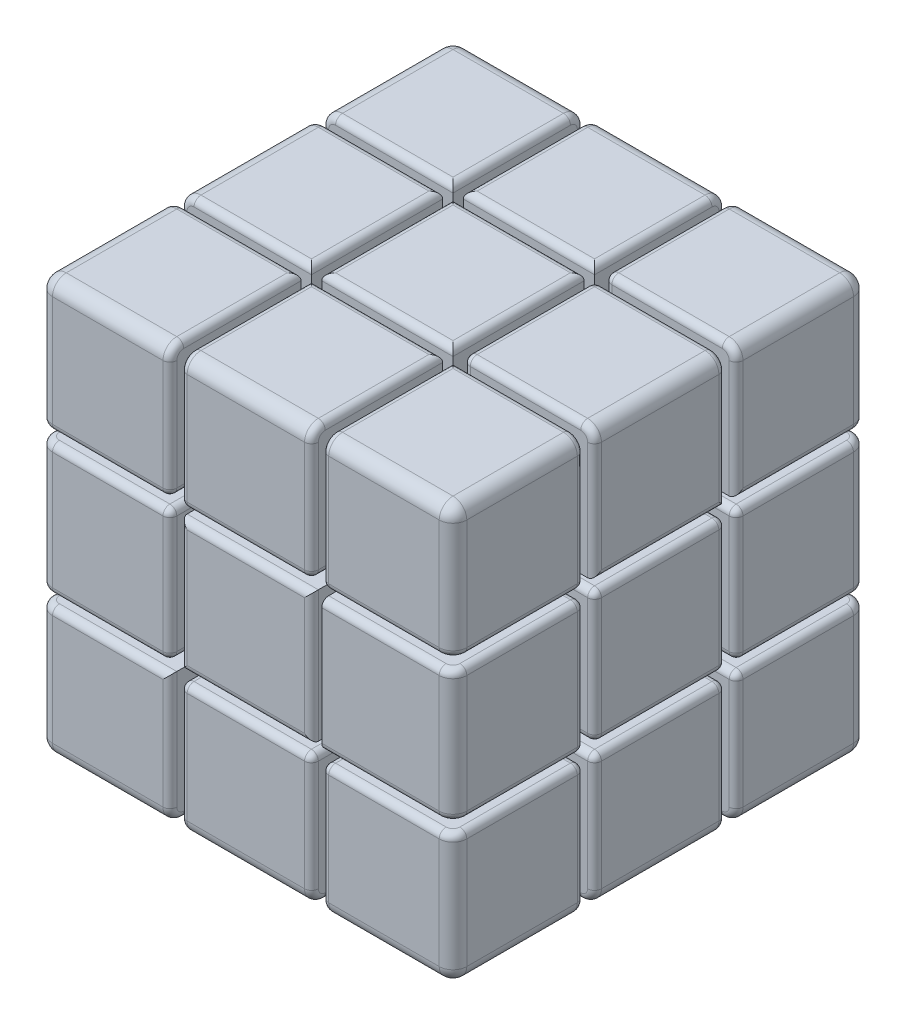
SolidWorks part; units mm, degrees
ref_plane "Front Plane" through (0, 0, 0) normal (0, 0, 1) x (1, 0, 0)
ref_plane "Top Plane" through (0, 0, 0) normal (0, 1, 0) x (1, 0, 0)
ref_plane "Right Plane" through (0, 0, 0) normal (1, 0, 0) x (0, 0, -1)
sketch "Sketch1" plane through (0, 0, 0) normal (0, 1, 0) x (1, 0, 0)
  line L1 (-30, 30) -> (30, 30)
  line L2 (-30, 30) -> (-30, -30)
  line L3 (-30, -30) -> (30, -30)
  line L4 (30, 30) -> (30, -30)
  line L5 (-30, 30) -> (30, -30) construction
  line L6 (-30, -30) -> (30, 30) construction
  point P0 (0, 0)
  dimension "D1" = 60
  dimension "D2" = 60
extrude "Boss-Extrude1" add sketch "Sketch1" along normal blind 60
sketch "Sketch2" plane through (0, 0, 30) normal (0, 0, 1) x (1, 0, 0)
  line L0 (-30, 60) -> (30, 60) construction
  line L1 (-11, 60) -> (-9.5, 60)
  line L2 (-11, 60) -> (-11, 0)
  line L3 (-11, 0) -> (-9.5, 0)
  line L4 (-9.5, 60) -> (-9.5, 0)
  line L5 (-30, 0) -> (30, 0) construction
  line L6 (-30, 60) -> (-30, 0) construction
  line L7 (9.5, 60) -> (11, 60)
  line L8 (9.5, 60) -> (9.5, 0)
  line L9 (9.5, 0) -> (11, 0)
  line L10 (11, 60) -> (11, 0)
  line L11 (-30, 41) -> (30, 41)
  line L12 (-30, 41) -> (-30, 39.5)
  line L13 (-30, 39.5) -> (30, 39.5)
  line L14 (30, 41) -> (30, 39.5)
  line L15 (30, 60) -> (30, 0) construction
  line L17 (-30, 20.5) -> (30, 20.5)
  line L18 (-30, 20.5) -> (-30, 19)
  line L19 (-30, 19) -> (30, 19)
  line L20 (30, 20.5) -> (30, 19)
  dimension "D1" = 1.5
  dimension "D2" = 1.5
  dimension "D3" = 1.5
  dimension "D4" = 1.5
  dimension "D5" = 19
  dimension "D6" = 19
  dimension "D7" = 19
  dimension "D8" = 19
extrude "Cut-Extrude1" cut sketch "Sketch2" against normal blind 60 contours L11 L14 L13 L12 | L2 L3 L4 L1 | L19 L20 L17 L18 | L8 L9 L10 L7
sketch "Sketch3" plane through (30, 0, 0) normal (1, 0, 0) x (0, 0, -1)
  line L0 (-30, 60) -> (30, 60) construction
  line L1 (-9.5, 60) -> (-11, 60)
  line L2 (-9.5, 60) -> (-9.5, 0)
  line L3 (-9.5, 0) -> (-11, 0)
  line L4 (-11, 60) -> (-11, 0)
  line L5 (-30, 0) -> (30, 0) construction
  line L6 (30, 0) -> (-30, 0) construction
  line L7 (9.5, 60) -> (11, 60)
  line L8 (9.5, 60) -> (9.5, 0)
  line L9 (9.5, 0) -> (11, 0)
  line L10 (11, 60) -> (11, 0)
  line L11 (30, 19) -> (30, 0) construction
  dimension "D1" = 19
  dimension "D2" = 1.5
  dimension "D3" = 1.5
  dimension "D4" = 19
extrude "Cut-Extrude2" cut sketch "Sketch3" against normal blind 60
fillet "Fillet1" radius 2 3 edges at (20.5, 60, 30) (30, 50.5, 30) (30, 60, 20.5)
fillet "Fillet2" radius 2 3 edges at (30, 0, 20.5) (20.5, 0, 30) (30, 9.5, 30)
fillet "Fillet3" radius 2 1 edges at (30, 30, 30)
fillet "Fillet4" radius 2 1 edges at (0, 60, 30)
fillet "Fillet5" radius 2 3 edges at (-30, 60, 20.5) (-30, 50.5, 30) (-20.5, 60, 30)
fillet "Fillet6" radius 2 3 edges at (-20.5, 0, 30) (-30, 0, 20.5) (-30, 9.5, 30)
fillet "Fillet7" radius 2 1 edges at (-30, 30, 30)
fillet "Fillet8" radius 2 1 edges at (0, 0, 30)
fillet "Fillet9" radius 2 1 edges at (-30, 60, 0)
fillet "Fillet10" radius 2 3 edges at (-20.5, 60, -30) (-30, 50.5, -30) (-30, 60, -20.5)
fillet "Fillet11" radius 2 1 edges at (-30, 30, -30)
fillet "Fillet12" radius 2 3 edges at (-30, 0, -20.5) (-20.5, 0, -30) (-30, 9.5, -30)
fillet "Fillet13" radius 2 1 edges at (-30, 0, 0)
fillet "Fillet14" radius 2 1 edges at (0, 0, -30)
fillet "Fillet15" radius 2 3 edges at (30, 9.5, -30) (30, 0, -20.5) (20.5, 0, -30)
fillet "Fillet16" radius 2 1 edges at (30, 0, 0)
fillet "Fillet17" radius 2 1 edges at (30, 30, -30)
fillet "Fillet18" radius 2 3 edges at (30, 60, -20.5) (20.5, 60, -30) (30, 50.5, -30)
fillet "Fillet19" radius 2 1 edges at (30, 60, 0)
fillet "Fillet20" radius 2 1 edges at (0, 60, -30)
fillet "Fillet21" radius 1 3 edges at (19.5, 19, 30) (29.4142, 19, 29.4142) (30, 19, 19.5)
fillet "Fillet22" radius 1 1 edges at (30, 19, 0)
fillet "Fillet23" radius 1 3 edges at (19.5, 39.5, 30) (29.4142, 39.5, 29.4142) (30, 39.5, 19.5)
fillet "Fillet24" radius 1 1 edges at (30, 39.5, 0)
fillet "Fillet25" radius 1 3 edges at (19.5, 39.5, -30) (29.4142, 39.5, -29.4142) (30, 39.5, -19.5)
fillet "Fillet26" radius 1 3 edges at (20, 39.5, -11) (29.7071, 39.2071, -11) (30, 29.5, -11)
fillet "Fillet27" radius 1 3 edges at (20, 39.5, 9.5) (29.7071, 39.2071, 9.5) (30, 29.5, 9.5)
fillet "Fillet28" radius 1 3 edges at (20, 39.5, 11) (29.7071, 39.2071, 11) (30, 29.5, 11)
fillet "Fillet29" radius 1 5 edges at (20, 20.5, 11) (29.7071, 20.5, 11.2929) (19.5, 20.5, 30) (29.4142, 20.5, 29.4142) (30, 20.5, 20)
fillet "Fillet30" radius 1 3 edges at (20, 20.5, 9.5) (29.7071, 20.5, 9.2071) (30, 20.5, -0.5)
fillet "Fillet31" radius 1 5 edges at (19.5, 20.5, -30) (29.4142, 20.5, -29.4142) (20, 20.5, -11) (29.7071, 20.5, -11.2929) (30, 20.5, -20)
fillet "Fillet32" radius 1 3 edges at (19.5, 19, -30) (29.4142, 19, -29.4142) (30, 19, -19.5)
fillet "Fillet33" radius 1 6 edges at (19.5, 41, -30) (29.4142, 41, -29.4142) (19.5, 60, -11) (29.4142, 59.4142, -11) (30, 41, -19.5) (30, 49.5, -11)
fillet "Fillet34" radius 1 7 edges at (19.5, 60, -9.5) (29.4142, 59.4142, -9.5) (19.5, 60, 9.5) (29.4142, 59.4142, 9.5) (30, 49.5, -9.5) (30, 41, 0) (30, 49.5, 9.5)
fillet "Fillet35" radius 1 4 edges at (-9.5, 60, 0) (0, 60, -9.5) (9.5, 60, 0) (0, 60, 9.5)
fillet "Fillet36" radius 1 5 edges at (11, 50, -9.5) (11, 59.7071, -9.2071) (11, 50, 9.5) (11, 59.7071, 9.2071) (11, 60, 0)
fillet "Fillet37" radius 1 6 edges at (30, 49.5, 11) (29.4142, 59.4142, 11) (11, 49.5, 30) (11, 59.4142, 29.4142) (19.5, 60, 11) (11, 60, 19.5)
fillet "Fillet38" radius 1 7 edges at (9.5, 49.5, 30) (9.5, 59.4142, 29.4142) (-9.5, 49.5, 30) (-9.5, 59.4142, 29.4142) (9.5, 60, 19.5) (-9.5, 60, 19.5) (0, 60, 11)
fillet "Fillet39" radius 1 6 edges at (-30, 49.5, 11) (-29.4142, 59.4142, 11) (-11, 49.5, 30) (-11, 59.4142, 29.4142) (-19.5, 60, 11) (-11, 60, 19.5)
fillet "Fillet40" radius 1 7 edges at (-30, 49.5, -9.5) (-29.4142, 59.4142, -9.5) (-30, 49.5, 9.5) (-29.4142, 59.4142, 9.5) (-19.5, 60, -9.5) (-19.5, 60, 9.5) (-11, 60, 0)
fillet "Fillet41" radius 1 6 edges at (-30, 49.5, -11) (-29.4142, 59.4142, -11) (-11, 49.5, -30) (-11, 59.4142, -29.4142) (-19.5, 60, -11) (-11, 60, -19.5)
fillet "Fillet42" radius 1 7 edges at (9.5, 49.5, -30) (9.5, 59.4142, -29.4142) (-9.5, 49.5, -30) (-9.5, 59.4142, -29.4142) (9.5, 60, -19.5) (0, 60, -11) (-9.5, 60, -19.5)
fillet "Fillet43" radius 1 7 edges at (11, 41, -20) (11, 41.2929, -29.7071) (11, 50, -30) (11, 59.4142, -29.4142) (11, 50, -11) (11, 59.7071, -11.2929) (11, 60, -20)
fillet "Fillet44" radius 1 8 edges at (11, 39.2071, -29.7071) (11, 39.5, -20.5) (11, 39.2071, -11.2929) (11, 30, -11) (11, 20.7929, -11.2929) (11, 20.5, -20.5) (11, 20.7929, -29.7071) (11, 30, -30)
fillet "Fillet45" radius 1 5 edges at (11, 19, -20) (11, 18.7071, -29.7071) (11, 0, -19.5) (11, 0.5858, -29.4142) (11, 10, -30)
fillet "Fillet46" radius 1 7 edges at (-9.5, 0, -19.5) (-9.5, 0.5858, -29.4142) (9.5, 0, -19.5) (9.5, 0.5858, -29.4142) (-9.5, 10.5, -30) (0, 19, -30) (9.5, 10.5, -30)
fillet "Fillet47" radius 1 6 edges at (-30, 19, -19.5) (-29.4142, 19, -29.4142) (-11, 0, -19.5) (-11, 0.5858, -29.4142) (-19.5, 19, -30) (-11, 10.5, -30)
fillet "Fillet48" radius 1 7 edges at (-30, 39.5, -19.5) (-29.4142, 39.5, -29.4142) (-30, 20.5, -19.5) (-29.4142, 20.5, -29.4142) (-19.5, 39.5, -30) (-11, 30, -30) (-19.5, 20.5, -30)
fillet "Fillet49" radius 1 4 edges at (0, 39.5, -30) (-9.5, 30, -30) (0, 20.5, -30) (9.5, 30, -30)
fillet "Fillet50" radius 1 5 edges at (-9.5, 41, -20) (-9.2071, 41, -29.7071) (9.5, 41, -20) (9.2071, 41, -29.7071) (0, 41, -30)
fillet "Fillet51" radius 1 7 edges at (-20, 41, -11) (-29.7071, 41, -11.2929) (-30, 41, -20) (-29.4142, 41, -29.4142) (-11, 41, -20) (-11.2929, 41, -29.7071) (-20, 41, -30)
fillet "Fillet52" radius 1 7 edges at (20, 41, 11) (29.7071, 41, 11.2929) (11, 41, 20) (11.2929, 41, 29.7071) (20, 41, 30) (29.4142, 41, 29.4142) (30, 41, 20)
fillet "Fillet53" radius 1 6 edges at (-11, 0, 19.5) (-11, 0.5858, 29.4142) (-30, 19, 19.5) (-29.4142, 19, 29.4142) (-11, 10.5, 30) (-19.5, 19, 30)
fillet "Fillet54" radius 1 7 edges at (-20, 41, 11) (-29.7071, 41, 11.2929) (-30, 41, 20) (-29.4142, 41, 29.4142) (-11, 41, 20) (-11.2929, 41, 29.7071) (-20, 41, 30)
fillet "Fillet55" radius 1 4 edges at (0, 39.5, 30) (9.5, 30, 30) (0, 20.5, 30) (-9.5, 30, 30)
fillet "Fillet56" radius 1 6 edges at (-30, 39.5, 19.5) (-29.4142, 39.5, 29.4142) (-30, 20.5, 19.5) (-29.4142, 20.5, 29.4142) (-19.5, 39.5, 30) (-19.5, 20.5, 30)
fillet "Fillet57" radius 1 5 edges at (-9.5, 41, 20) (-9.2071, 41, 29.7071) (9.5, 41, 20) (9.2071, 41, 29.7071) (0, 41, 30)
fillet "Fillet58" radius 1 5 edges at (-20, 20.5, -11) (-29.7071, 20.7929, -11) (-20, 39.5, -11) (-29.7071, 39.2071, -11) (-30, 30, -11)
fillet "Fillet59" radius 1 7 edges at (-11, 10, -11) (-11.2929, 0.2929, -11) (-20, 0, -11) (-29.4142, 0.5858, -11) (-20, 19, -11) (-29.7071, 18.7071, -11) (-30, 10, -11)
fillet "Fillet60" radius 1 7 edges at (-19.5, 0, 9.5) (-29.4142, 0.5858, 9.5) (-19.5, 0, -9.5) (-29.4142, 0.5858, -9.5) (-30, 19, 0) (-30, 10.5, 9.5) (-30, 10.5, -9.5)
fillet "Fillet61" radius 1 4 edges at (-30, 30, -9.5) (-30, 39.5, 0) (-30, 30, 9.5) (-30, 20.5, 0)
fillet "Fillet62" radius 1 5 edges at (-20, 41, -9.5) (-29.7071, 41, -9.2071) (-20, 41, 9.5) (-29.7071, 41, 9.2071) (-30, 41, 0)
fillet "Fillet63" radius 1 5 edges at (-20, 39.5, 11) (-29.7071, 39.2071, 11) (-20, 20.5, 11) (-29.7071, 20.7929, 11) (-30, 30, 11)
fillet "Fillet64" radius 1 11 edges at (20, 19, 9.5) (29.7071, 18.7071, 9.5) (30, 10, 9.5) (29.4142, 0.5858, 9.5) (20, 19, -9.5) (29.7071, 18.7071, -9.5) (30, 10, -9.5) (29.4142, 0.5858, -9.5) (11, 0, 0) (19.5, 0, 9.5) (19.5, 0, -9.5)
fillet "Fillet65" radius 1 4 edges at (0, 0, -9.5) (-9.5, 0, 0) (0, 0, 9.5) (9.5, 0, 0)
fillet "Fillet66" radius 1 5 edges at (-11, 10, -9.5) (-11, 0.2929, -9.2071) (-11, 10, 9.5) (-11, 0.2929, 9.2071) (-11, 0, 0)
fillet "Fillet67" radius 1 8 edges at (11.2929, 0.2929, -11) (11, 9.5, -11) (11.2929, 18.7071, -11) (20.5, 19, -11) (29.7071, 18.7071, -11) (30, 10, -11) (29.4142, 0.5858, -11) (20, 0, -11)
fillet "Fillet68" radius 1 5 edges at (-9.5, 10, -11) (-9.2071, 0.2929, -11) (9.5, 10, -11) (9.2071, 0.2929, -11) (0, 0, -11)
fillet "Fillet69" radius 1 10 edges at (11, 19, 20) (11, 18.7071, 29.7071) (11, 10, 30) (11, 0.5858, 29.4142) (20, 19, 11) (29.7071, 18.7071, 11) (30, 10, 11) (29.4142, 0.5858, 11) (11, 0, 19.5) (19.5, 0, 11)
fillet "Fillet70" radius 1 7 edges at (-9.5, 10.5, 30) (-9.5, 0.5858, 29.4142) (9.5, 10.5, 30) (9.5, 0.5858, 29.4142) (0, 0, 11) (-9.5, 0, 19.5) (9.5, 0, 19.5)
fillet "Fillet71" radius 1 5 edges at (-9.5, 19, 20) (-9.2071, 19, 29.7071) (9.5, 19, 20) (9.2071, 19, 29.7071) (0, 19, 30)
fillet "Fillet72" radius 1 5 edges at (20, 39.5, -9.5) (29.7071, 39.2071, -9.5) (20, 20.5, -9.5) (29.7071, 20.7929, -9.5) (30, 30, -9.5)
fillet "Fillet73" radius 1 8 edges at (-11, 39.2071, 29.7071) (-11, 39.5, 20.5) (-11, 39.2071, 11.2929) (-11, 30, 11) (-11, 20.7929, 11.2929) (-11, 20.5, 20.5) (-11, 20.7929, 29.7071) (-11, 30, 30)
